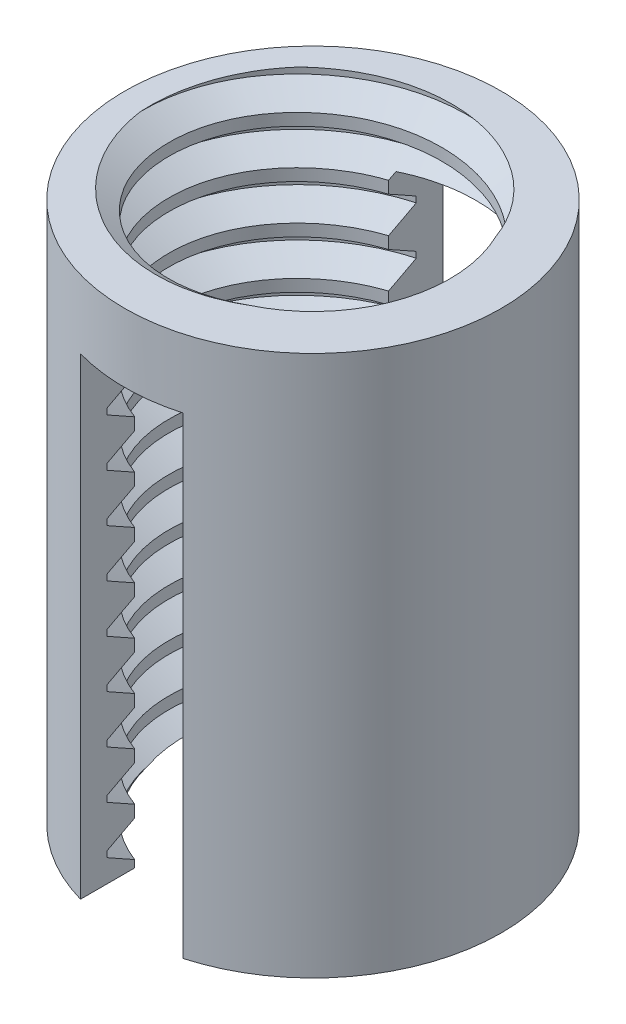
SolidWorks part; units mm, degrees
ref_plane "Front Plane" through (0, 0, 0) normal (0, 0, 1) x (1, 0, 0)
ref_plane "Top Plane" through (0, 0, 0) normal (0, 1, 0) x (1, 0, 0)
ref_plane "Right Plane" through (0, 0, 0) normal (1, 0, 0) x (0, 0, -1)
sketch "Sketch1" plane through (0, 0, 0) normal (0, 1, 0) x (1, 0, 0)
  circle A0 centre (0, 0) radius 2.75
  circle A1 centre (0, 0) radius 2
  dimension "D1" = 5.5
  dimension "D2" = 4
extrude "Boss-Extrude1" add sketch "Sketch1" along normal blind 7.9
sketch "Sketch2" plane through (0, 0, 0) normal (0, -1, 0) x (1, 0, 0)
  line L1 (-0.75, 2.75) -> (0.75, 2.75)
  line L2 (-0.75, 2.75) -> (-0.75, -2.75)
  line L3 (-0.75, -2.75) -> (0.75, -2.75)
  line L4 (0.75, 2.75) -> (0.75, -2.75)
  line L5 (-0.75, 2.75) -> (0.75, -2.75) construction
  line L6 (-0.75, -2.75) -> (0.75, 2.75) construction
  circle A0 centre (0, 0) radius 2.75 construction
  point P0 (0, 0)
  dimension "D1" = 1.5
extrude "Cut-Extrude1" cut sketch "Sketch2" against normal blind 6.9
thread "Thread1" pitch 0.7 method cut profile "Thread Profile1" start angle 0, offset 1, length 10, pitch 0.7, diameter 4
ref_plane "Plane1" through (-2, 8.9, 0) normal (0, 0, 1) x (-1, 0, 0)
sketch "Thread Profile1" plane through (-2, 8.9, 0) normal (0, 0, 1) x (-1, 0, 0)
  line L0 (0, 0) -> (0, 0.7) construction
  line L1 (0, 0) -> (0.3789, 0.2187)
  line L2 (0.3789, 0.2187) -> (0.3789, 0.3062)
  line L3 (0.3789, 0.3062) -> (0, 0.525)
  line L4 (0.3789, 0.2625) -> (0, 0.2625) construction
  line L11 (0, 0) -> (0, 0.525)
  point P2 (0, 0)
  dimension "Pitch" = 0.7
  dimension "Profile_Angle" = 60
  dimension "Profile_Land" = 0.0875
  dimension "Profile_Height" = 0.3789
